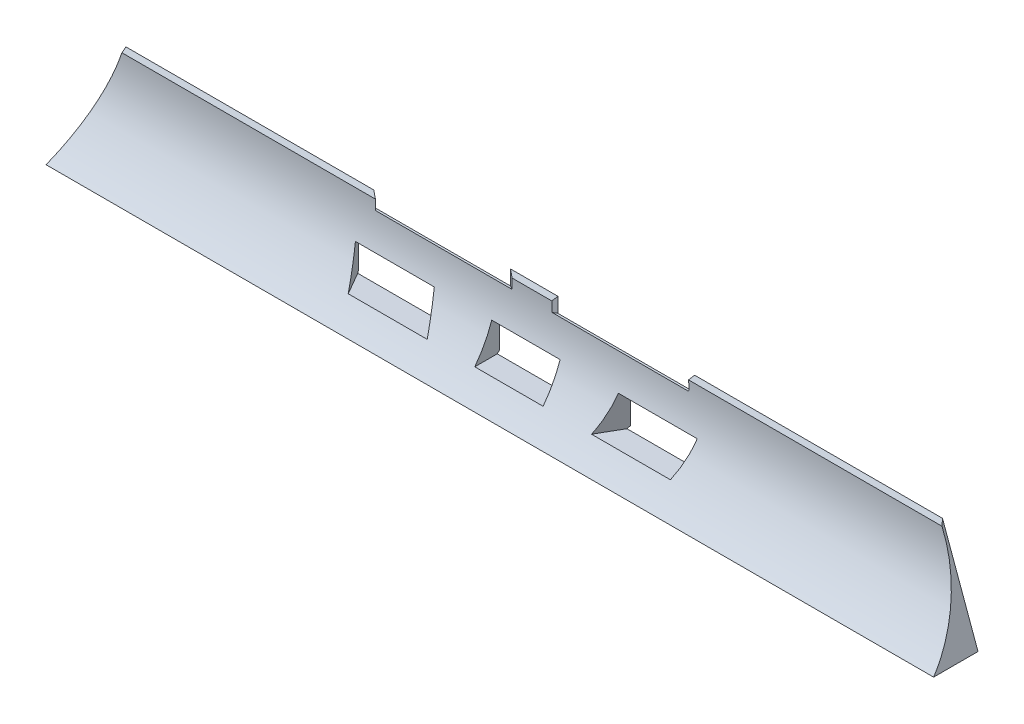
SolidWorks part; units mm, degrees
material "ABS"
ref_plane "Front Plane" through (0, 0, 0) normal (0, 0, 1) x (1, 0, 0)
ref_plane "Top Plane" through (0, 0, 0) normal (0, 1, 0) x (1, 0, 0)
ref_plane "Right Plane" through (0, 0, 0) normal (1, 0, 0) x (0, 0, -1)
sketch "Sketch1" plane through (0, 0, 0) normal (1, 0, 0) x (0, 0, -1)
  line L0 (0, 0) -> (-10, 0)
  line L1 (-10, 0) -> (0, 22)
  line L2 (0, 22) -> (0, 0)
  dimension "D1" = 10
  dimension "D2" = 22
extrude "Boss-Extrude1" add sketch "Sketch1" along normal blind 200
sketch "Sketch2" plane through (200, 0, 0) normal (1, 0, 0) x (0, 0, -1)
  line L0 (0, 22) -> (-10, 0) construction
  line L1 (-10, 0) -> (0, 0) construction
  line L2 (0, 0) -> (0, 22) construction
  line L3 (-10, 0) -> (-0.5, 20.9)
  arc A0 (-10, 0) -> (-0.5, 20.9) centre (-25.4682, 19.6401) ccw
  dimension "D3" = 25
  dimension "D1" = 0
  dimension "D2" = 0.5
extrude "Cut-Extrude1" cut sketch "Sketch2" against normal through all
sketch "Sketch4" plane through (200, 0, 0) normal (1, 0, 0) x (0, 0, -1)
  line L0 (-5, 0) -> (0, 5)
  line L1 (-10, 0) -> (0, 0) construction
  line L2 (0, 0) -> (0, 22) construction
  line L3 (0, 5) -> (0, 0)
  line L4 (0, 0) -> (-5, 0)
  dimension "D1" = 5
  dimension "D2" = 5
extrude "Cut-Extrude2" cut sketch "Sketch4" against normal through all
sketch "Sketch5" plane through (0, 0, 0) normal (0, 0, -1) x (-1, 0, 0)
  line L0 (0, 0) -> (-200, 0) construction
  line L1 (-200, 5) -> (-197, 5)
  line L2 (-200, 5) -> (-200, 0)
  line L3 (-200, 0) -> (-197, 0)
  line L4 (-197, 5) -> (-197, 0)
  dimension "D1" = 3
extrude "Boss-Extrude2" add sketch "Sketch5" against normal up to surface up to face at (100, 2.5, 2.5)
ref_plane "Plane1" through (100, 0, 0) normal (1, 0, 0) x (0, 0, -1)
sketch "Sketch6" plane through (0, 0, 0) normal (0, 0, -1) x (-1, 0, 0)
  line L0 (-200, 22) -> (-191.9927, 22)
  line L1 (-200, 22) -> (0, 22) construction
  line L2 (-191.9927, 22) -> (-200, 0)
  line L3 (-200, 22) -> (-200, 0)
  dimension "D1" = 20
extrude "Cut-Extrude3" cut sketch "Sketch6" against normal through all
mirror "Mirror2" about plane through (100, 0, 0) normal (1, 0, 0) of "Cut-Extrude3", "Boss-Extrude2"
sketch "Sketch7" plane through (0, 0, 0) normal (0, 0, -1) x (-1, 0, 0)
  line L1 (-159.8316, 13.465) -> (-167.8316, 13.465)
  line L2 (-159.8316, 13.465) -> (-159.8316, 2.465)
  line L3 (-159.8316, 2.465) -> (-167.8316, 2.465)
  line L4 (-167.8316, 13.465) -> (-167.8316, 2.465)
  line L5 (-160.8316, 13.465) -> (-166.8316, 13.465) construction
  line L6 (-166.8316, 2.465) -> (-160.8316, 2.465) construction
  line L7 (-166.8316, 13.465) -> (-166.8316, 2.465) construction
  dimension "D1" = 8
  dimension "D2" = 1
extrude "Boss-Extrude3" add sketch "Sketch7" against normal up to next
sketch "Sketch8" plane through (0, 0, 0) normal (0, 0, -1) x (-1, 0, 0)
  line L1 (-165.5637, 8.5) -> (-167.2957, 5.5)
  line L2 (-167.2957, 5.5) -> (-165.5637, 2.5)
  line L3 (-165.5637, 2.5) -> (-162.0995, 2.5)
  line L4 (-162.0995, 2.5) -> (-160.3675, 5.5)
  line L5 (-160.3675, 5.5) -> (-162.0995, 8.5)
  line L6 (-162.0995, 8.5) -> (-165.5637, 8.5)
  line L7 (-167.8316, 0) -> (-159.8316, 0) construction
  line L8 (-165.3316, 10.465) -> (-165.3316, 5.465) construction
  circle A2 centre (-163.8316, 5.5) radius 3 construction
  point P13 (-163.8316, 8.5)
  dimension "D1" = 6
  dimension "D2" = 1.5
  dimension "D3" = 5.5
extrude "Cut-Extrude4" cut sketch "Sketch8" against normal blind 1.8 contours L5 L6 L1 L2 L3 L4 | L1 L2 L3 L4 L5 L6 region at (163.8316, 5.5, 0)
mirror "Mirror3" about plane through (100, 0, 0) normal (1, 0, 0) of "Cut-Extrude4", "Boss-Extrude3"
sketch "Sketch9" plane through (0, 0, 0) normal (0, 0, 1) x (1, 0, 0)
  line L1 (92.2158, 4.465) -> (107.6158, 4.465)
  line L2 (92.2158, 4.465) -> (92.2158, 11.665)
  line L3 (92.2158, 11.665) -> (107.6158, 11.665)
  line L4 (107.6158, 4.465) -> (107.6158, 11.665)
extrude "Cut-Extrude6" cut sketch "Sketch9" along normal through all
ref_plane "Plane2" through (32.136, 0, -55.6612) normal (-0.5, 0, 0.866) x (0.866, 0, 0.5)
sketch "Sketch10" plane through (32.136, 0, -55.6612) normal (-0.5, 0, 0.866) x (0.866, 0, 0.5)
  line L1 (105.439, 4.465) -> (120.839, 4.465)
  line L2 (105.439, 4.465) -> (105.439, 11.665)
  line L3 (105.439, 11.665) -> (120.839, 11.665)
  line L4 (120.839, 4.465) -> (120.839, 11.665)
extrude "Cut-Extrude8" cut sketch "Sketch10" along normal blind 15.8 and the other way blind 6.8
ref_plane "Plane3" through (115.6697, 0, -66.7819) normal (-0.866, 0, 0.5) x (0.5, 0, 0.866)
sketch "Sketch11" plane through (115.6697, 0, -66.7819) normal (-0.866, 0, 0.5) x (0.5, 0, 0.866)
  line L1 (68.0717, 27.465) -> (52.6717, 27.465)
  line L2 (68.0717, 27.465) -> (68.0717, 18.665)
  line L3 (68.0717, 18.665) -> (52.6717, 18.665)
  line L4 (52.6717, 27.465) -> (52.6717, 18.665)
  line L7 (52.6717, 27.465) -> (52.6717, 20.265) construction
  line L8 (47.1217, 18.665) -> (73.6217, 18.665) construction
extrude "Cut-Extrude9" cut sketch "Sketch11" along normal blind 97.8
mirror "Mirror4" about plane through (100, 0, 0) normal (1, 0, 0) of "Cut-Extrude8", "Cut-Extrude9"
